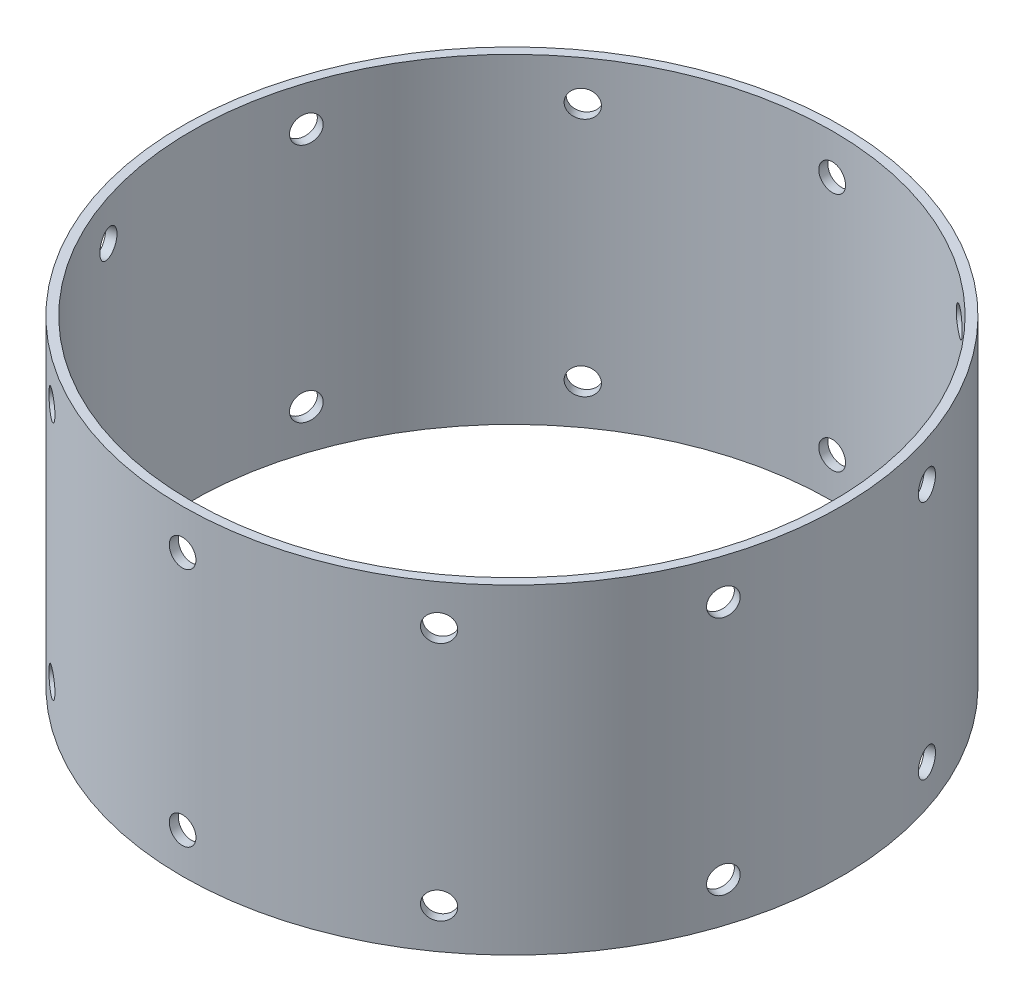
SolidWorks part; units mm, degrees
material "Fiberglass"
ref_plane "Front Plane" through (0, 0, 0) normal (0, 0, 1) x (1, 0, 0)
ref_plane "Top Plane" through (0, 0, 0) normal (0, 1, 0) x (1, 0, 0)
ref_plane "Right Plane" through (0, 0, 0) normal (1, 0, 0) x (0, 0, -1)
sketch "Sketch1" plane through (0, 0, 0) normal (0, 1, 0) x (1, 0, 0)
  circle A0 centre (0, 0) radius 76.2
  circle A1 centre (0, 0) radius 78.359
  dimension "D1" = 152.4
  dimension "D2" = 156.718
extrude "Boss-Extrude1" add sketch "Sketch1" along normal blind 76.2
sketch "Sketch2" plane through (0, 0, 0) normal (0, 0, 1) x (1, 0, 0)
  line L0 (0, 0) -> (0, 234.7266) construction
  line L1 (-76.2, 0) -> (76.2, 0) construction
  line L2 (-78.359, 0) -> (78.359, 0) construction
  line L3 (78.359, 38.1) -> (-54.7898, 38.1) construction
  line L4 (78.359, 0) -> (78.359, 76.2) construction
  circle A0 centre (0, 9.525) radius 3.175
  circle A1 centre (0, 66.675) radius 3.175
  dimension "D1" = 9.525
extrude "Cut-Extrude1" cut sketch "Sketch2" against normal through all
ref_axis "Axis1" through (0, 0, 0) along (0, 1, 0)
pattern_circular "CirPattern1" count 10 over 360 about axis through (0, 0, 0) along (0, 1, 0) of "Cut-Extrude1"
